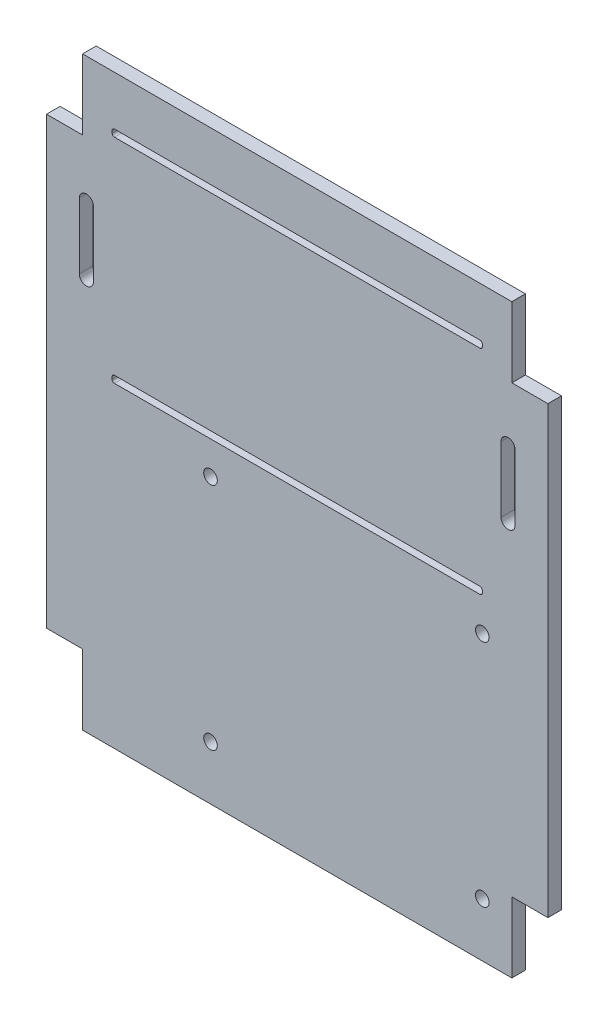
SolidWorks part; units mm, degrees
ref_plane "Front Plane" through (0, 0, 0) normal (0, 0, 1) x (1, 0, 0)
ref_plane "Top Plane" through (0, 0, 0) normal (0, 1, 0) x (1, 0, 0)
ref_plane "Right Plane" through (0, 0, 0) normal (1, 0, 0) x (0, 0, -1)
sketch "Sketch1" plane through (0, 0, 0) normal (0, 0, 1) x (1, 0, 0)
  line L4 (0, 0) -> (0, 75.1224) construction
  line L5 (-53.5, 0) -> (-45.802, 0)
  line L6 (-53.5, 0) -> (-53.5, 95)
  line L7 (-53.5, 95) -> (-45.802, 95)
  line L8 (53.5, 0) -> (53.5, 95)
  line L9 (0, 76) -> (24.7187, 76) construction
  line L10 (-42.5, 55) -> (42.5, 55) construction
  line L11 (-42.5, 55) -> (-42.5, 97) construction
  line L12 (48, 57.5289) -> (48, -67.5733) construction
  line L13 (-48, 50.1534) -> (-48, -79.2411) construction
  line L14 (-42.5, 97) -> (42.5, 97) construction
  line L15 (39.5, -70.263) -> (39.5, 45.5) construction
  line L16 (43, 49) -> (-42, 49) construction
  line L17 (43, 49) -> (43, -7) construction
  line L18 (43, -7) -> (-42, -7) construction
  line L19 (-42, 49) -> (-42, -7) construction
  line L20 (43, 49) -> (-42, -7) construction
  line L21 (43, -7) -> (-42, 49) construction
  line L22 (39.5, -3.5) -> (-18.5, -3.5) construction
  line L23 (39.5, 45.5) -> (-18.5, 45.5) construction
  line L24 (45.802, 95) -> (53.5, 95)
  line L26 (45.802, 95) -> (45.802, 110)
  line L27 (45.802, 110) -> (-45.802, 110)
  line L28 (-45.802, 95) -> (-45.802, 110)
  line L29 (42.5, 55) -> (42.5, 97) construction
  line L30 (-42.5, 55) -> (42.5, 97) construction
  line L31 (-42.5, 97) -> (42.5, 55) construction
  line L32 (-39, 98) -> (39, 98)
  line L33 (-39.5, 98.5) -> (-39.5, 99)
  line L34 (-39, 99.5) -> (39, 99.5)
  line L35 (39.5, 98.5) -> (39.5, 99)
  line L36 (-39.5, 98) -> (39.5, 99.5) construction
  line L37 (-39.5, 99.5) -> (39.5, 98) construction
  line L38 (-39, 52.5) -> (39, 52.5)
  line L39 (39.5, 53.5) -> (39.5, 53)
  line L40 (-39, 54) -> (39, 54)
  line L41 (-39.5, 53.5) -> (-39.5, 53)
  line L43 (0, 76) -> (0, 98.4165) construction
  line L44 (-45, 83) -> (-45, 69) construction
  line L45 (-43.5, 83) -> (-43.5, 69)
  line L46 (-46.5, 83) -> (-46.5, 69)
  line L47 (45, 83) -> (45, 69) construction
  line L50 (43.5, 83) -> (43.5, 69)
  line L51 (46.5, 83) -> (46.5, 69)
  line L52 (-45.802, -15) -> (-45.802, 0)
  line L53 (-45.802, -15) -> (45.802, -15)
  line L54 (45.802, -15) -> (45.802, 0)
  line L55 (45.802, 0) -> (53.5, 0)
  line L56 (0, -15) -> (0, -11.0192) construction
  circle A0 centre (39.5, -3.5) radius 1.45
  circle A1 centre (39.5, 45.5) radius 1.45
  circle A2 centre (-18.5, -3.5) radius 1.45
  circle A3 centre (-18.5, 45.5) radius 1.45
  arc A4 (39, 98) -> (39.5, 98.5) centre (39, 98.5) ccw
  arc A5 (39, 99.5) -> (39.5, 99) centre (39, 99) cw
  arc A6 (-39.5, 98.5) -> (-39, 98) centre (-39, 98.5) ccw
  arc A7 (-39, 99.5) -> (-39.5, 99) centre (-39, 99) ccw
  arc A8 (39, 52.5) -> (39.5, 53) centre (39, 53) ccw
  arc A9 (39, 54) -> (39.5, 53.5) centre (39, 53.5) cw
  arc A10 (-39.5, 53.5) -> (-39, 54) centre (-39, 53.5) cw
  arc A11 (-39, 52.5) -> (-39.5, 53) centre (-39, 53) cw
  arc A12 (-43.5, 83) -> (-46.5, 83) centre (-45, 83) ccw
  arc A13 (-46.5, 69) -> (-43.5, 69) centre (-45, 69) ccw
  arc A16 (43.5, 83) -> (46.5, 83) centre (45, 83) cw
  arc A17 (46.5, 69) -> (43.5, 69) centre (45, 69) cw
  point P0 (0, 0)
  point P5 (0, 98.75)
  point P12 (0.5, 21)
  point P15 (0.5, 21)
  point P31 (-18.5, 1.5)
  point P32 (0, 39.5291)
  point P43 (0, 76)
  point P70 (0, 0)
  point P73 (-45, 76)
  point P82 (45, 76)
  point P91 (0, 26)
  dimension "D3" = 5.5
  dimension "D10" = 2.9
  dimension "D11" = 2.9
  dimension "D13" = 2.9
  dimension "D14" = 2.9
  dimension "D23" = 0.5
  dimension "D1" = 107
  dimension "D2" = 95
  dimension "D4" = 5.5
  dimension "D5" = 7.698
  dimension "D6" = 56
  dimension "D7" = 3.5
  dimension "D8" = 3.5
  dimension "D9" = 49
  dimension "D12" = 58
  dimension "D15" = 58
  dimension "D16" = 0.5
  dimension "D17" = 15
  dimension "D18" = 7.698
  dimension "D19" = 85
  dimension "D20" = 85
  dimension "D21" = 42
  dimension "D22" = 1
  dimension "D24" = 6
  dimension "D25" = 7
  dimension "D26" = 1.5
  dimension "D27" = 1
  dimension "D28" = 3
  dimension "D29" = 7
  dimension "D30" = 15
extrude "Boss-Extrude2" add sketch "Sketch1" along normal blind 2.9
